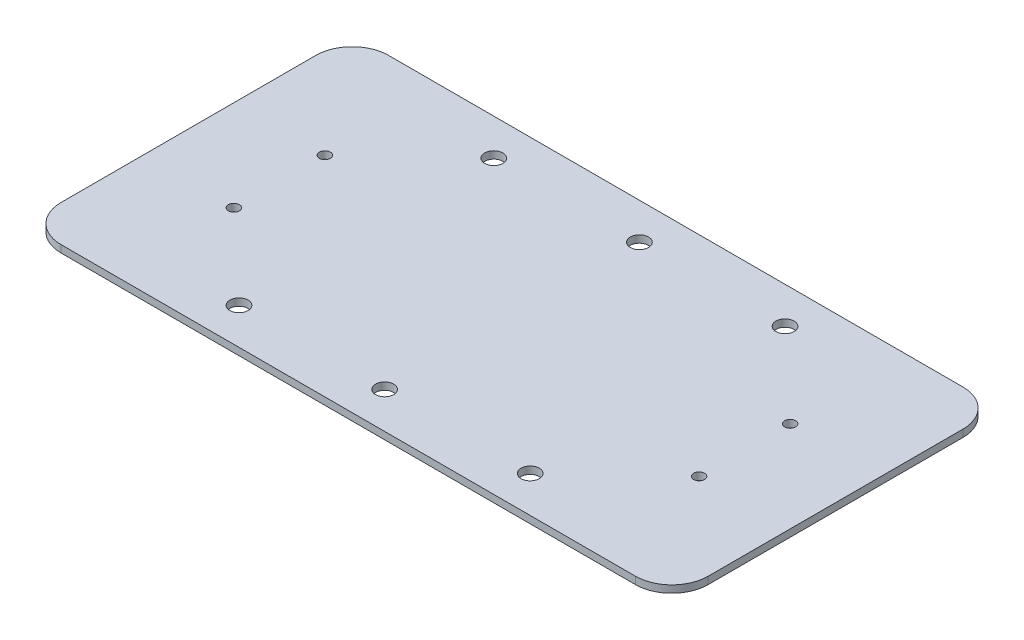
SolidWorks part; units mm, degrees
ref_plane "Front Plane" through (0, 0, 0) normal (0, 0, 1) x (1, 0, 0)
ref_plane "Top Plane" through (0, 0, 0) normal (0, 1, 0) x (1, 0, 0)
ref_plane "Right Plane" through (0, 0, 0) normal (1, 0, 0) x (0, 0, -1)
sketch "Sketch1" plane through (0, 0, 0) normal (0, 1, 0) x (1, 0, 0)
  line L0 (0, -35) -> (0, 35)
  line L1 (-88.9, -45) -> (88.9, -45)
  line L2 (-88.9, -45) -> (-88.9, 45)
  line L3 (-88.9, 45) -> (88.9, 45)
  line L4 (88.9, -45) -> (88.9, 45)
  line L5 (-88.9, -45) -> (88.9, 45) construction
  line L6 (-88.9, 45) -> (88.9, -45) construction
  line L7 (-88.9, 0) -> (88.9, 0) construction
  line L8 (40, -35) -> (40, 35)
  line L9 (-40, -35) -> (-40, 35)
  circle A0 centre (0, 35) radius 2.5
  circle A1 centre (0, -35) radius 2.5
  circle A2 centre (40, 35) radius 2.5
  circle A3 centre (40, -35) radius 2.5
  circle A4 centre (-40, 35) radius 2.5
  circle A5 centre (-40, -35) radius 2.5
  point P0 (0, 0)
  point P9 (0, 0)
  dimension "D4" = 5
  dimension "D1" = 177.8
  dimension "D2" = 90
  dimension "D3" = 70
  dimension "D7" = 40
  dimension "D8" = 40
  dimension "D5" = 2
  dimension "D6" = 2
extrude "Boss-Extrude1" add sketch "Sketch1" along normal blind 2 contours L1 L4 L3 L2 A1 A0 region at (-86.9072, 0, 0)
fillet "Fillet1" radius 10 4 edges at (88.9, 1, 45) (88.9, 1, -45) (-88.9, 1, -45) (-88.9, 1, 45)
sketch "Sketch2" plane through (0, 0, 0) normal (0, -1, 0) x (1, 0, 0)
  line L1 (-78.9, 25) -> (-48.9, 25)
  line L2 (-78.9, 25) -> (-78.9, -25) construction
  line L3 (-78.9, -25) -> (-48.9, -25)
  line L4 (88.9, -35) -> (88.9, 35)
  line L5 (78.9, 45) -> (-78.9, 45)
  line L6 (-88.9, 35) -> (-88.9, -35)
  line L7 (-78.9, -45) -> (78.9, -45)
  line L8 (88.9, -35) -> (88.9, 35)
  line L9 (78.9, 45) -> (-78.9, 45)
  line L10 (-88.9, 35) -> (-88.9, -35)
  line L11 (-78.9, -45) -> (78.9, -45)
  line L12 (-48.9, 25) -> (-48.9, -25)
  line L13 (48.9, 25) -> (78.9, 25)
  line L14 (48.9, 25) -> (48.9, -25)
  line L15 (48.9, -25) -> (78.9, -25)
  line L16 (78.9, 25) -> (78.9, -25)
  line L24 (-78.9, 0) -> (-48.9, 0)
  line L25 (-78.9, 25) -> (-78.9, 0)
  line L26 (0, 45) -> (0, -45)
  circle A0 centre (-63.9, 12.5) radius 1.5
  circle A1 centre (-63.9, -12.5) radius 1.5
  circle A2 centre (63.9, -12.5) radius 1.5
  circle A3 centre (63.9, 12.5) radius 1.5
  arc A4 (88.9, 35) -> (78.9, 45) centre (78.9, 35) ccw
  arc A5 (-78.9, 45) -> (-88.9, 35) centre (-78.9, 35) ccw
  arc A6 (-88.9, -35) -> (-78.9, -45) centre (-78.9, -35) ccw
  arc A7 (78.9, -45) -> (88.9, -35) centre (78.9, -35) ccw
  arc A8 (88.9, 35) -> (78.9, 45) centre (78.9, 35) ccw
  arc A9 (-78.9, 45) -> (-88.9, 35) centre (-78.9, 35) ccw
  arc A10 (-88.9, -35) -> (-78.9, -45) centre (-78.9, -35) ccw
  arc A11 (78.9, -45) -> (88.9, -35) centre (78.9, -35) ccw
  point P20 (-78.9, 0)
  point P21 (-88.9, 0)
  point P22 (48.9, 0)
  point P27 (-78.9, 12.5)
  point P28 (-63.9, 0)
  dimension "D6" = 3
  dimension "D2" = 30
  dimension "D3" = 50
  dimension "D4" = 10
  dimension "D5" = 10
  dimension "D1" = 0
extrude "Cut-Extrude1" cut sketch "Sketch2" against normal up to surface (2 mm away) contours A0 | A1 | A3 | A2 region at (-63.9, 0, 12.5) region at (-63.9, 0, -12.5) region at (63.9, 0, -12.5) region at (63.9, 0, 12.5) up to face at (0, 2, -32.5)
equation "\"D\"=70"
equation "\"D3@Sketch1\"=\"D\""
